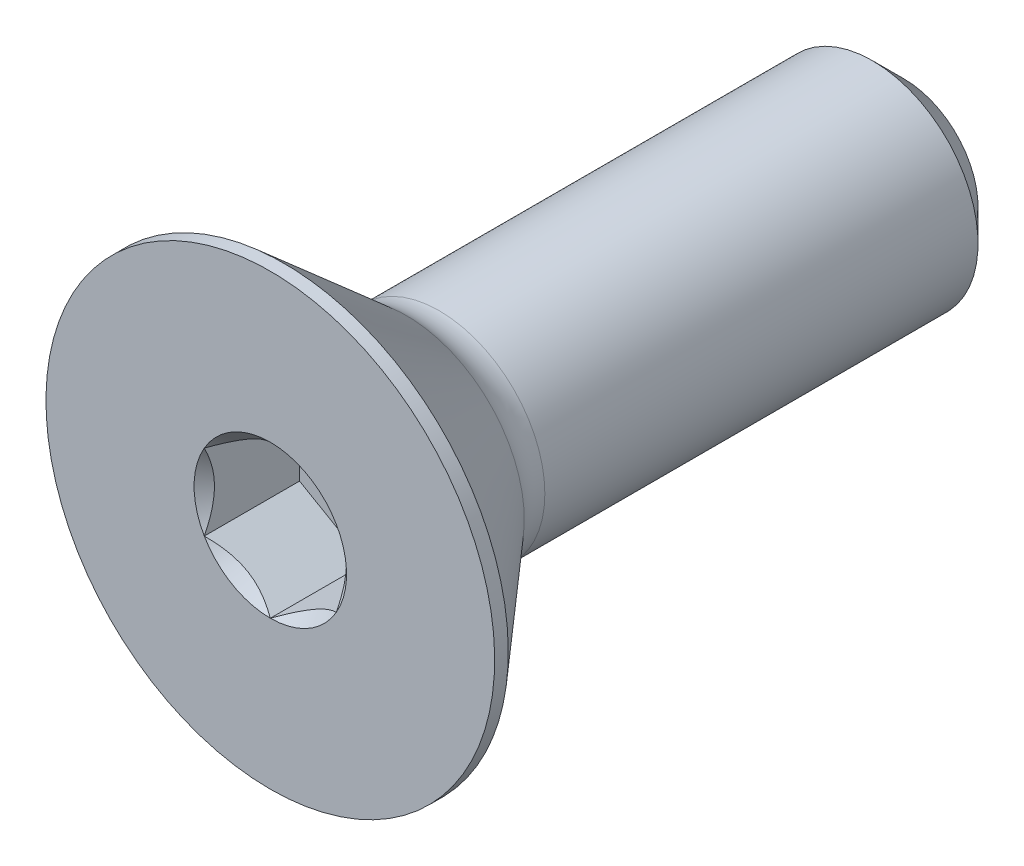
SolidWorks part; units mm, degrees
ref_plane "Front" through (0, 0, 0) normal (0, 0, 1) x (1, 0, 0)
ref_plane "Top" through (0, 0, 0) normal (0, 1, 0) x (1, 0, 0)
ref_plane "Right" through (0, 0, 0) normal (1, 0, 0) x (0, 0, -1)
sketch "Sketch1" plane through (0, 0, 0) normal (1, 0, 0) x (0, 0, -1)
  line L0 (0, 6.7437) -> (0.4089, 6.7437) construction
  line L1 (0.4089, 6.7437) -> (4.0894, 3.5443) construction
  line L2 (0, 3.175) -> (19.05, 3.175)
  line L3 (19.05, 3.175) -> (19.05, 0)
  line L4 (19.05, 0) -> (0, 0)
  line L5 (0, 0) -> (0, 6.7437) construction
  line L6 (0, 6.7437) -> (0, -6.7437) construction
  line L7 (19.05, 3.175) -> (19.05, -3.175) construction
  line L8 (0, -6.7437) -> (0.4089, -6.7437) construction
  line L9 (0.4089, -6.7437) -> (4.0894, -3.5443) construction
  line L11 (0, 3.175) -> (0, 0)
  line L12 (5.0772, 3.175) -> (5.0772, 0) construction
  arc A1 (4.0894, 3.5443) -> (5.0772, 3.175) centre (5.0772, 4.6807) ccw construction
  dimension "D1" = 0.4089
revolve "Revolve1" add sketch "Sketch1" angle 360 mid plane about L4
sketch "Sketch3" plane through (0, 0, -19.05) normal (0, 0, -1) x (-1, 0, 0)
  circle A0 centre (0, 0) radius 3.175
curve "Helix/Spiral1" pitch 1.27 height 19.05 turns 15
sketch "Sketch2" plane through (0, 0, 0) normal (1, 0, 0) x (0, 0, -1)
  line L0 (19.05, 3.175) -> (20.1612, 3.175)
  line L1 (20.1612, 3.175) -> (19.685, 2.3501)
  line L2 (19.685, 2.3501) -> (19.5262, 2.3501)
  line L3 (19.5262, 2.3501) -> (19.05, 3.175)
  line L4 (19.2881, 2.7626) -> (19.9231, 2.7626) construction
  dimension "D1" = 60
  dimension "D2" = 0.1588
  dimension "D3" = 0.635
chamfer "Chamfer1" distance 0.9525 angle 45 1 edges at (0, 3.175, -19.05)
sweep "Cut-Sweep1" [suppressed] cut profiles "Sketch2" path "Helix/Spiral1"
sketch "Sketch7" plane through (0, 0, 0) normal (1, 0, 0) x (0, 0, -1)
  line L0 (0, 6.7437) -> (0.4089, 6.7437) construction
  line L1 (0.4089, 6.7437) -> (4.0894, 3.5443) construction
  line L2 (0, 6.7437) -> (0.4089, 6.7437)
  line L3 (0.4089, 6.7437) -> (4.0894, 3.5443)
  line L4 (5.0772, 3.175) -> (5.0772, 0) construction
  line L5 (5.0772, 3.175) -> (5.0772, 0)
  line L7 (0, 0) -> (0, 6.7437) construction
  line L8 (0, 0) -> (0, 6.7437)
  line L9 (0, 0) -> (5.0772, 0)
  line L10 (7.4181, 0) -> (-7.4181, 0) construction
  arc A0 (4.0894, 3.5443) -> (5.0772, 3.175) centre (5.0772, 4.6807) ccw construction
  arc A1 (4.0894, 3.5443) -> (5.0772, 3.175) centre (5.0772, 4.6807) ccw
revolve "Revolve2" add sketch "Sketch7" angle 360 mid plane about L9
ref_plane "Plane1" through (0, 0, -5.0772) normal (0, 0, 1) x (1, 0, 0)
sketch "Sketch8" plane through (0, 0, -5.0772) normal (0, 0, 1) x (1, 0, 0)
  circle A0 centre (0, 0) radius 3.175
extrude "Boss-Extrude1" add sketch "Sketch8" against normal through all draft 45
sketch "Sketch11" [suppressed] plane through (0, 0, 0) normal (1, 0, 0) x (0, 0, -1)
  line L0 (4.4996, 0) -> (-4.4996, 0) construction
  line L1 (7.3025, 3.8989) -> (1.7272, 3.8989)
  line L2 (7.3025, 3.8989) -> (7.3025, -3.8989)
  line L3 (7.3025, -3.8989) -> (1.7272, -3.8989)
  line L4 (1.7272, 3.8989) -> (1.7272, -3.8989)
  line L5 (0, 3.8989) -> (0.1727, 3.8989) construction
  line L7 (4.7625, 1.7526) -> (4.7625, 0) construction
  point P4 (1.7272, 0)
  dimension "D1" = 2.54
extrude "Cut-Extrude4" [suppressed] cut sketch "Sketch11" against normal through all and the other way through all
combine bodies "Combine1" operation type add bodies to combine 117 108
sketch "Sketch5" plane through (0, 0, 0) normal (0, 0, 1) x (1, 0, 0)
  line L1 (1.9844, -1.1457) -> (1.9844, 1.1457)
  line L2 (1.9844, 1.1457) -> (0, 2.2914)
  line L3 (0, 2.2914) -> (-1.9844, 1.1457)
  line L4 (-1.9844, 1.1457) -> (-1.9844, -1.1457)
  line L5 (-1.9844, -1.1457) -> (0, -2.2914)
  line L6 (0, -2.2914) -> (1.9844, -1.1457)
  circle A0 centre (0, 0) radius 1.9844 construction
  dimension "Hex" = 3.9688
extrude "Cut-Extrude2" cut sketch "Sketch5" against normal blind 2.8626
sketch "Sketch6" plane through (0, 0, 0) normal (0, 0, 1) x (1, 0, 0)
  circle A0 centre (0, 0) radius 2.2914
extrude "Cut-Extrude3" cut sketch "Sketch6" against normal blind 2.8626 draft 45
sketch "Sketch9" [suppressed] plane through (0, 0, -5.0772) normal (0, 0, 1) x (1, 0, 0)
  circle A1 centre (0, 0) radius 3.175
  circle A2 centre (0, 0) radius 3.175
  point P0 (0, 3.175)
  dimension "D1" = 0
extrude "Boss-Extrude2" [suppressed] add sketch "Sketch9" against normal offset from surface (20.3228 mm away) 22.225 up to face at (0, 2.2225, -19.05)
sketch "Sketch10" plane through (0, 0, 0) normal (1, 0, 0) x (0, 0, -1)
  line L0 (19.05, 3.175) -> (19.05, -3.175) construction
  point P0 (17.145, -3.175)
  dimension "D1" = 1.905
equation "\"D3@Helix/Spiral1\" = \"Lg@Sketch1\""
equation "\"D2@Sketch2\" = \"D4@Helix/Spiral1\" * .125"
equation "\"D3@Sketch2\" = \"D4@Helix/Spiral1\" * .5"
equation "\"D1@Chamfer1\" = \"D4@Helix/Spiral1\" * .75"
equation "\"D1@Cut-Extrude2\" = \"Head Ht@Sketch1\" * .7"
equation "\"D1@Sketch1\" = \"Head Ht@Sketch1\" * .1"
equation "\"D1@Sketch10\" = \"D4@Helix/Spiral1\" * 1.5"
equation "\"D1@Cut-Extrude3\" = \"D1@Cut-Extrude2\""
